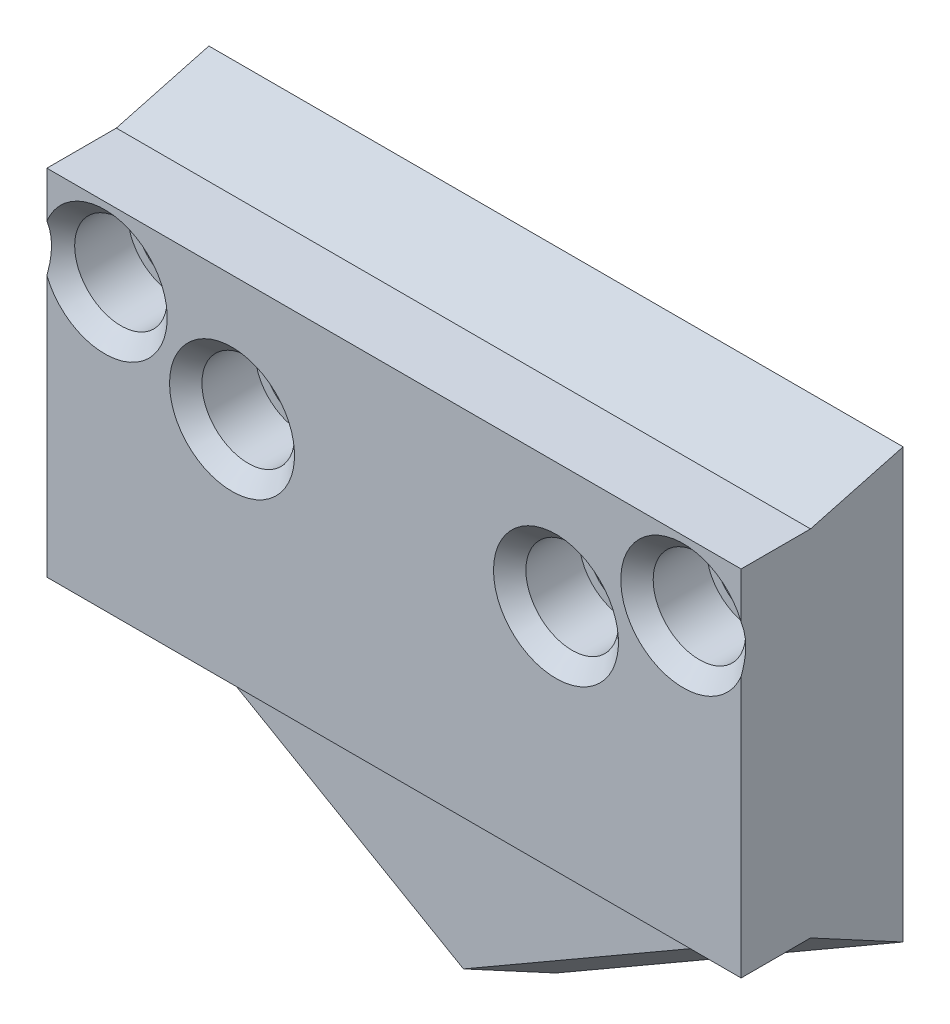
SolidWorks part; units mm, degrees
ref_plane "Plano frontal" through (0, 0, 0) normal (0, 0, 1) x (1, 0, 0)
ref_plane "Plano superior" through (0, 0, 0) normal (0, 1, 0) x (1, 0, 0)
ref_plane "Plano direito" through (0, 0, 0) normal (1, 0, 0) x (0, 0, -1)
sketch "Esboço1" plane through (0, 0, 0) normal (0, 0, 1) x (1, 0, 0)
  line L0 (-15, 28) -> (-15, 8.6603)
  line L1 (-15, 8.6603) -> (0, 0)
  line L2 (0, 0) -> (0, 28) construction
  line L3 (15, 28) -> (-15, 28)
  line L4 (15, 8.6603) -> (0, 0)
  line L5 (15, 28) -> (15, 8.6603)
  dimension "D1" = 120
  dimension "D2" = 30
  dimension "D3" = 28
extrude "Ressalto-extrusão1" add sketch "Esboço1" along normal blind 4
chamfer "Chanfro1" distance 5 angle 25 2 edges at (-7.5, 4.3301, 4) (7.5, 4.3301, 4) first distance on face at (-7.5, 4.3301, 2) first distance on face at (7.5, 4.3301, 2)
chamfer "Chanfro2" distance 5 angle 15 1 edges at (0, 28, 4) first distance on face at (0, 28, 2)
sketch "Esboço2" plane through (0, 0, 4) normal (0, 0, 1) x (1, 0, 0)
  line L0 (15, 26.6603) -> (-15, 26.6603) construction
  line L1 (-15, 11.3525) -> (15, 11.3525)
  line L2 (-15, 11.3525) -> (-15, 26.6603)
  line L3 (-15, 26.6603) -> (15, 26.6603)
  line L4 (15, 11.3525) -> (15, 26.6603)
  line L5 (-15, 11.3525) -> (15, 26.6603) construction
  line L6 (-15, 26.6603) -> (15, 11.3525) construction
  line L7 (0, 2.6922) -> (15, 11.3525) construction
  point P0 (0, 19.0064)
  dimension "D1" = 30
extrude "Ressalto-extrusão2" add sketch "Esboço2" along normal blind 3
sketch "Esboço3" plane through (0, 0, 0) normal (0, 0, 1) x (1, 0, 0)
  line L0 (0, 0) -> (0, 25.7319) construction
  line L1 (15, 26.6603) -> (-15, 26.6603) construction
  line L3 (-9.3246, 23.6603) -> (-10.9123, 26.4103) construction
  line L4 (-10.9123, 26.4103) -> (-14.0877, 26.4103) construction
  line L5 (-14.0877, 26.4103) -> (-15.6754, 23.6603) construction
  line L6 (-15.6754, 23.6603) -> (-14.0877, 20.9103) construction
  line L7 (-14.0877, 20.9103) -> (-10.9123, 20.9103) construction
  line L8 (-10.9123, 20.9103) -> (-9.3246, 23.6603) construction
  circle A0 centre (-7, 21.2623) radius 1.6
  circle A1 centre (7, 21.2623) radius 1.6
  circle A2 centre (-12.5, 23.6603) radius 1.6
  circle A3 centre (12.5, 23.6603) radius 1.6
  circle A4 centre (-7, 21.2623) radius 2.75 construction
  circle A5 centre (-12.5, 23.6603) radius 2.75 construction
  point P13 (-12.5, 19.6875)
  point P22 (0, 0)
  point P23 (-12.5, 19.3301)
  point P24 (-12.5, 24.235)
  dimension "D2" = 3.2
  dimension "D5" = 5.5
  dimension "D6" = 5.5
  dimension "D7" = 0.5
  dimension "D1" = 14
  dimension "D3" = 3
  dimension "D4" = 25
extrude "Corte-extrusão1" cut sketch "Esboço3" along normal through all both and the other way through all
sketch "Esboço4" plane through (0, 0, 0) normal (0, 0, -1) x (-1, 0, 0)
  line L0 (0, 0) -> (0, 23.2948) construction
  circle A2 centre (-7, 21.2623) radius 2
  circle A4 centre (12.5, 23.6603) radius 2
  circle A5 centre (-12.5, 23.6603) radius 2
  circle A6 centre (7, 21.2623) radius 2
  dimension "D2" = 4
extrude "Corte-extrusão2" cut sketch "Esboço4" along normal blind 3 from surface starting at face at (10.9, 23.6603, 7)
sketch "Esboço6" plane through (0, 0, 0) normal (0, 0, -1) x (-1, 0, 0)
  line L1 (-2.25, 20) -> (2.25, 20)
  line L2 (-2.25, 20) -> (-2.25, 5)
  line L3 (-2.25, 5) -> (2.25, 5)
  line L4 (2.25, 20) -> (2.25, 5)
  line L5 (-2.25, 20) -> (2.25, 5) construction
  line L6 (-2.25, 5) -> (2.25, 20) construction
  point P0 (0, 12.5)
  dimension "D1" = 4.5
  dimension "D2" = 15
  dimension "D3" = 5
extrude "Corte-extrusão3" cut sketch "Esboço6" against normal blind 3
chamfer "Chanfro3" distance 0.7 angle 45 4 edges at (10.5, 23.6603, 7) (5, 21.2623, 7) (-14.5, 23.6603, 7) (-9, 21.2623, 7)
